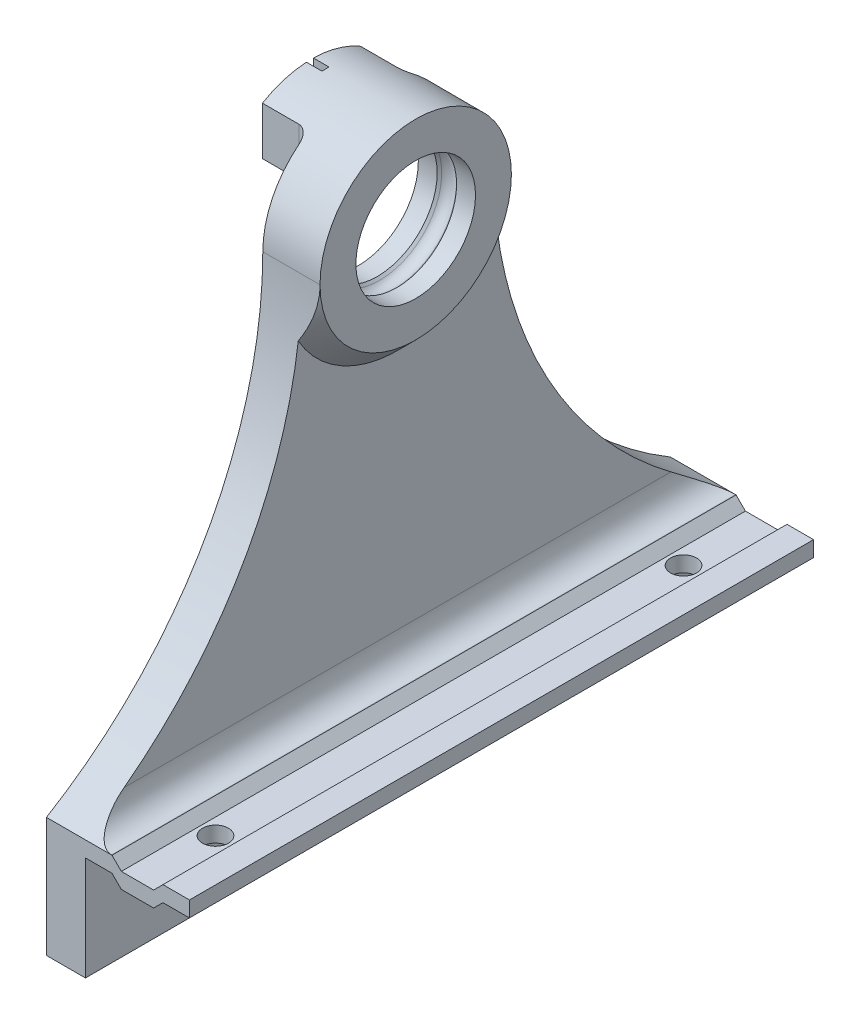
SolidWorks part; units mm, degrees
ref_plane "Front Plane" through (0, 0, 0) normal (0, 0, 1) x (1, 0, 0)
ref_plane "Top Plane" through (0, 0, 0) normal (0, 1, 0) x (1, 0, 0)
ref_plane "Right Plane" through (0, 0, 0) normal (1, 0, 0) x (0, 0, -1)
sketch "Sketch1" plane through (0, 0, 0) normal (0, 0, 1) x (1, 0, 0)
  line L0 (10, 26) -> (10, 20) construction
  line L5 (0, 0) -> (20, 0) construction
  line L6 (0, 0) -> (0, 20) construction
  line L7 (0, 20) -> (20, 20) construction
  line L8 (20, 0) -> (20, 20) construction
  line L9 (5.1, 122) -> (14.9, 122) construction
  line L10 (5.1, 122) -> (5.1, 26) construction
  line L11 (5.1, 26) -> (14.9, 26) construction
  line L12 (14.9, 122) -> (14.9, 26) construction
  line L13 (5.1, 122) -> (14.9, 26) construction
  line L14 (5.1, 26) -> (14.9, 122) construction
  line L15 (10, 74) -> (50010, 74) construction
  point P4 (10, 74)
  point P14 (14.9, 26)
  dimension "D1" = 20
  dimension "D2" = 96
  dimension "D3" = 9.8
  dimension "D4" = 6
sketch "Sketch2" plane through (0, 0, 0) normal (1, 0, 0) x (0, 0, -1)
  line L0 (-60, 0) -> (60, 0)
  line L1 (0, 0) -> (-54890.8777, 0) construction
  line L2 (-82.83, 20) -> (54808.0478, 20) construction
  line L3 (0, 122) -> (0, 26) construction
  line L4 (-83.1115, 96.39) -> (49916.8885, 96.39) construction
  line L5 (90.3268, 123.67) -> (50090.3268, 123.67) construction
  line L6 (103.2777, 30) -> (50103.2777, 30) construction
  line L7 (-104.869, 57.28) -> (49895.131, 57.28) construction
  line L8 (-60, 0) -> (-60, 23)
  line L9 (60, 0) -> (60, 23)
  circle A1 centre (0, 96.39) radius 11.5
  circle A2 centre (0, 96.39) radius 18.4 construction
  arc A3 (-18.4, 96.39) -> (18.4, 96.39) centre (0, 96.39) cw
  arc A4 (-18.4, 96.39) -> (-60, 23) centre (-103.9367, 96.39) cw
  arc A5 (18.4, 96.39) -> (60, 23) centre (103.9367, 96.39) ccw
  point P4 (0, 0)
  point P27 (0, 0)
  point P28 (0, 0)
  dimension "D3" = 93.67
  dimension "D4" = 23
  dimension "D5" = 36.8
  dimension "D9" = 23
  dimension "D1" = 20
  dimension "D2" = 120
  dimension "D6" = 27.28
  dimension "D7" = 27.28
  dimension "D8" = 10
  dimension "D10" = 23
extrude "Boss-Extrude1" add sketch "Sketch2" against normal blind 7.5
sketch "Sketch3" plane through (0, 0, 0) normal (1, 0, 0) x (0, 0, -1)
  circle A0 centre (0, 96.39) radius 18.4
  circle A1 centre (0, 96.39) radius 11.5
extrude "Boss-Extrude2" add sketch "Sketch3" along normal blind 3.5
chamfer "Chamfer1" distance 3.5 angle 45 1 edges at (0, 77.99, 0)
ref_axis "Axis1" through (-7.5, 96.39, 0) along (1, 0, 0)
sketch "Sketch5" plane through (0, 0, 0) normal (0, 0, 1) x (1, 0, 0)
  line L0 (-7.5, 106.89) -> (3.5, 106.89) construction
  line L1 (-3.4319, 108.3219) -> (-3.8638, 107.89)
  line L2 (-3.8638, 107.89) -> (-0.1362, 107.89)
  line L5 (-7.5, 114.79) -> (-7.5, 96.39) construction
  line L6 (3.5, 96.39) -> (3.5, 114.79) construction
  line L7 (-7.5, 96.39) -> (3.5, 96.39) construction
  line L10 (-7.5, 107.89) -> (3.5, 107.89) construction
  line L11 (-2, 104.89) -> (-2, 50104.89) construction
  line L12 (-0.5681, 108.3219) -> (-0.1362, 107.89)
  circle A0 centre (-2, 106.89) radius 2 construction
  arc A1 (-3.4319, 108.3219) -> (-0.5681, 108.3219) centre (-2, 106.89) cw
  dimension "D2" = 4
  dimension "D3" = 1
  dimension "D4" = 2.025
  dimension "D5" = 45
  dimension "D1" = 10.5
revolve "Cut-Revolve1" cut sketch "Sketch5" angle 360 about axis through (-7.5, 96.39, 0) along (1, 0, 0)
sketch "Sketch6" plane through (0, 0, 0) normal (1, 0, 0) x (0, 0, -1)
  line L1 (-60, 0) -> (60, 0) construction
  line L2 (-60, 0) -> (-60, 20) construction
  line L3 (-60, 20) -> (60, 20) construction
  line L4 (60, 0) -> (60, 20) construction
  line L5 (-60, 20) -> (60, 20)
  line L6 (-60, 20) -> (-60, 23)
  line L7 (-60, 23) -> (60, 23)
  line L8 (60, 20) -> (60, 23)
  dimension "D1" = 20
  dimension "D2" = 120
extrude "Boss-Extrude3" add sketch "Sketch6" along normal blind 20
fillet "Fillet1" radius 5 1 edges at (0, 23, 0)
sketch "Sketch7" plane through (0, 0, -60) normal (0, 0, -1) x (-1, 0, 0)
  line L0 (-14.9, 20) -> (-5.1, 20)
  line L1 (0, 20) -> (-20, 20) construction
  line L2 (-14.9, 20) -> (-13.1, 18.2)
  line L3 (-5.1, 20) -> (-6.9, 18.2)
  line L4 (-13.1, 18.2) -> (-6.9, 18.2)
  line L5 (-10, 20) -> (-10, 14.0333) construction
  point P6 (-10, 20)
  point P11 (0, 0)
  point P12 (-10, 18.2)
  point P14 (0, 0)
  point P15 (0, 0)
  dimension "D1" = 9.8
  dimension "D2" = 6.2
  dimension "D3" = 45
  dimension "D4" = 45
  dimension "D5" = 1.8
extrude "Boss-Extrude4" add sketch "Sketch7" against normal blind 120
sketch "Sketch8" plane through (0, 0, -60) normal (0, 0, -1) x (-1, 0, 0)
  line L0 (-25.5308, 21.2) -> (-22.3661, 21.2) construction
  line L1 (-14.9, 23) -> (-5.1, 23)
  line L3 (-20, 23) -> (-5, 23) construction
  line L4 (-13.1, 21.2) -> (-6.9, 21.2)
  line L7 (-13.1, 21.2) -> (-14.9, 23)
  line L8 (-6.9, 21.2) -> (-5.1, 23)
  line L10 (-10, 26) -> (-10, 20) construction
  point P5 (-10, 21.2)
  point P21 (-10, 21.2)
  dimension "D1" = 1.8
  dimension "D2" = 6.2
  dimension "D3" = 135
  dimension "D4" = 135
extrude "Cut-Extrude2" cut sketch "Sketch8" against normal through all
sketch "Sketch9" plane through (0, 23, 0) normal (0, 1, 0) x (1, 0, 0)
  line L0 (-77.8845, 0) -> (49922.1155, 0) construction
  line L2 (10, -60) -> (10, -45) construction
  line L3 (-7.5, 60) -> (10, 60) construction
  line L4 (-7.5, 60) -> (-7.5, 45) construction
  line L5 (-7.5, 45) -> (10, 45) construction
  line L6 (10, 60) -> (10, 45) construction
  line L7 (-7.5, -45) -> (10, -45) construction
  line L8 (-7.5, -60) -> (-7.5, -45) construction
  line L9 (-7.5, -60) -> (10, -60) construction
  circle A0 centre (10, 45) radius 2.5
  circle A1 centre (10, -45) radius 2.5
  dimension "D1" = 15
  dimension "D2" = 17.5
extrude "Cut-Extrude3" cut sketch "Sketch9" against normal through all
sketch "Sketch10" plane through (-7.5, 0, 0) normal (-1, 0, 0) x (0, 0, 1)
  line L0 (0, 37.0118) -> (0, -49962.9882) construction
  line L2 (48, 0) -> (48, 10) construction
  line L3 (-60, 0) -> (-48, 0) construction
  line L4 (-60, 0) -> (-60, 10) construction
  line L5 (-60, 10) -> (-48, 10) construction
  line L6 (-48, 0) -> (-48, 10) construction
  line L7 (60, 10) -> (48, 10) construction
  line L8 (60, 0) -> (60, 10) construction
  line L9 (60, 0) -> (48, 0) construction
  circle A0 centre (-48, 10) radius 2.5
  circle A1 centre (48, 10) radius 2.5
  circle A2 centre (0, 10) radius 2.5
  dimension "D3" = 5
  dimension "D1" = 10
  dimension "D2" = 12
extrude "Cut-Extrude4" cut sketch "Sketch10" against normal through all
sketch "Sketch12" plane through (-7.5, 0, 0) normal (-1, 0, 0) x (0, 0, 1)
  line L0 (-0.3541, 59.1498) -> (-0.3541, 112.1498) construction
  line L1 (0, 84.89) -> (0, 59.19) construction
  line L2 (0, 26) -> (0, 122) construction
  line L3 (0, 122) -> (0, 26) construction
  line L4 (9.4666, 102.9194) -> (9.4666, 112.1679)
  line L5 (-8.5413, 66.0955) -> (9.3587, 66.0955)
  line L6 (-8.5413, 66.0955) -> (-8.5413, 59.1955)
  line L7 (-8.5413, 59.1955) -> (9.3587, 59.1955)
  line L8 (9.3587, 66.0955) -> (9.3587, 59.1955)
  line L9 (-9.4016, 112.2067) -> (-9.4016, 103.0126)
  circle A0 centre (0, 96.39) radius 11.5 construction
  arc A1 (-9.4016, 103.0126) -> (9.4666, 102.9194) centre (0, 96.39) cw
  arc A2 (-9.4016, 112.2067) -> (9.4666, 112.1679) centre (0, 96.39) cw
  arc A3 (18.4, 96.39) -> (-18.4, 96.39) centre (0, 96.39) ccw construction
  dimension "D1" = 53
  dimension "D2" = 25.7
  dimension "D3" = 17.9
  dimension "D4" = 6.9
extrude "Boss-Extrude5" add sketch "Sketch12" along normal blind 9
fillet "Fillet2" radius 9 3 edges at (-7.5, 62.6455, 9.3587) (-7.5, 62.6455, -8.5413) (-7.5, 59.1955, 0.4087)
fillet "Fillet3" radius 2 2 edges at (-7.5, 107.6097, -9.4016) (-7.5, 107.5437, 9.4666)
sketch "Sketch13" plane through (-16.5, 0, 0) normal (-1, 0, 0) x (0, 0, 1)
  line L0 (0.6, 59.3524) -> (0.6, 112.3524) construction
  line L1 (0, 122) -> (0, 26) construction
  line L6 (1.0109, 116.0306) -> (-0.3302, 116.0306)
  line L17 (1.0109, 116.0306) -> (1.0109, 104.454)
  line L18 (1.0109, 104.454) -> (-0.3302, 104.454)
  line L19 (-0.3302, 116.0306) -> (-0.3302, 104.454)
  line L20 (1.3008, 67.1573) -> (0, 67.1573)
  line L21 (1.3008, 67.1573) -> (1.3008, 57.6625)
  line L22 (1.3008, 57.6625) -> (0, 57.6625)
  line L23 (0, 67.1573) -> (0, 57.6625)
  circle A0 centre (-4.4594, 109.812) radius 1.85
  circle A1 centre (5.2056, 109.8619) radius 1.85
  circle A2 centre (-4.1586, 61.9802) radius 1.85
  circle A3 centre (5.4966, 61.953) radius 1.85
  arc M2 (-9.4016, 103.0126) -> (9.4666, 102.9194) centre (0, 96.39) cw
  arc M4 (9.4666, 112.1679) -> (-9.4016, 112.2067) centre (0, 96.39) ccw
  dimension "D3" = 3.7
  dimension "D4" = 3.7
  dimension "D5" = 3.7
  dimension "D1" = 53
extrude "Cut-Extrude6" cut sketch "Sketch13" against normal blind 6 contours A2 | A3 | A1 | A0 region at (-16.5, 109.812, -4.4594) region at (-16.5, 109.8619, 5.2056) region at (-16.5, 61.9802, -4.1586) region at (-16.5, 61.953, 5.4966)
extrude "Cut-Extrude8" cut sketch "Sketch13<4>" against normal blind 3 contours L20 L23 L22 L21 | L19 L17 M4 M2 | L18 L0 L19 M2 | L0 L18 L17 M2 | L6 L19 L17 M4 region at (-16.5, 106.17, 0.1347) region at (-16.5, 106.1576, 0.8051) region at (-16.5, 62.4099, 0.6504) region at (-16.5, 111.3306, 0.3406) region at (-16.5, 115.4067, 0.3426)
sketch "Sketch13<4>" plane through (-16.5, 0, 0) normal (-1, 0, 0) x (0, 0, 1) same geometry as "Sketch13"
